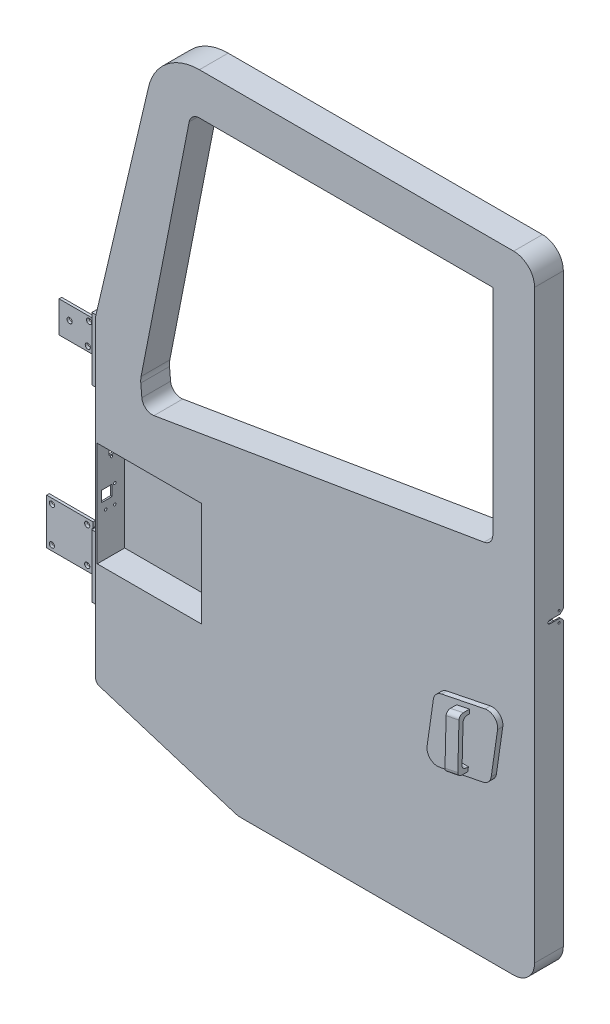
SolidWorks part; units mm, degrees
ref_plane "Front Plane" through (0, 0, 0) normal (0, 0, 1) x (1, 0, 0)
ref_plane "Top Plane" through (0, 0, 0) normal (0, 1, 0) x (1, 0, 0)
ref_plane "Right Plane" through (0, 0, 0) normal (1, 0, 0) x (0, 0, -1)
sketch "Sketch2" plane through (0, 0, 0) normal (0, 0, 1) x (1, 0, 0)
  line L1 (-179.7693, -762.022) -> (482.6, -762.022)
  line L3 (-281.2299, 761.978) -> (482.6, 761.978)
  line L4 (533.4, -711.222) -> (533.4, 711.178)
  line L5 (-459.8603, -656.939) -> (-452.0517, -645.784) construction
  line L6 (-417.9715, 597.0829) -> (44.2876, -63.266) construction
  line L8 (-524.4721, -657.2008) -> (-194.8579, -759.7295)
  line L9 (-306.1723, 639.7777) -> (-423.0219, 45.4039)
  line L10 (-423.7768, 31.1096) -> (-421.1458, 1.4921)
  line L14 (-281.2299, 660.378) -> (431.8, 660.378)
  line L16 (431.7996, 138.4174) -> (431.8, 660.378)
  line L17 (431.8, -660.422) -> (431.8, 660.378) construction
  line L18 (-172.0509, -660.422) -> (431.8, -660.422) construction
  line L19 (-533.4, 116.926) -> (-405.8883, 659.253)
  line L20 (-367.7549, -599.547) -> (-172.0509, -660.422) construction
  line L21 (-55.7209, -79.6007) -> (521.0599, 744.3665) construction
  line L22 (-306.1723, 639.7777) -> (-424.4164, 38.3105) construction
  line L23 (-424.4164, 38.3105) -> (-367.7549, -599.547) construction
  line L24 (-414.3579, -691.4526) -> (-194.8579, -759.7295) construction
  line L25 (-179.7693, -762.022) -> (482.6, -762.022)
  line L27 (-281.2299, 761.978) -> (482.6, 761.978)
  line L28 (533.4, -711.222) -> (533.4, 711.178)
  line L29 (-459.8603, -656.939) -> (-452.0517, -645.784) construction
  line L30 (-417.9715, 597.0829) -> (44.2876, -63.266) construction
  line L31 (-533.4, 116.926) -> (-466.2749, -638.723) construction
  line L32 (-391.6402, -21.3099) -> (410.6048, 113.3679)
  line L33 (-55.7209, -79.6007) -> (521.0599, 744.3665) construction
  line L34 (-281.2299, 761.978) -> (482.6, 761.978)
  line L35 (-533.4, 116.926) -> (-533.4, -645.074)
  line L36 (-179.7693, -762.022) -> (482.6, -762.022)
  line L37 (533.4, 711.178) -> (533.4, -711.222)
  line L38 (-417.9715, 597.0829) -> (44.2876, -63.266) construction
  line L39 (-471.5639, -673.6583) -> (-452.0517, -645.784) construction
  line L40 (-405.8883, 659.253) -> (-528.8132, 33.9764) construction
  line L41 (-55.7209, -79.6007) -> (521.0599, 744.3665) construction
  arc A0 (-405.8883, 659.253) -> (-281.2299, 761.978) centre (-281.2299, 634.978) cw
  arc A3 (533.4, 711.178) -> (482.6, 761.978) centre (482.6, 711.178) ccw
  arc A4 (482.6, -762.022) -> (533.4, -711.222) centre (482.6, -711.222) ccw
  arc A5 (-194.8579, -759.7295) -> (-179.7693, -762.022) centre (-179.7693, -711.222) ccw
  arc A7 (-367.7549, -599.547) -> (-367.7549, -599.547) centre (-367.7549, -599.547) ccw
  arc A8 (-172.0509, -660.422) -> (-172.0509, -660.422) centre (-172.0509, -660.422) ccw
  arc A9 (431.8, -660.422) -> (431.8, -660.422) centre (431.8, -660.422) ccw
  arc A10 (431.8, 660.378) -> (431.8, 660.378) centre (431.8, 660.378) ccw
  arc A11 (-306.1723, 639.7777) -> (-281.2299, 660.378) centre (-281.2299, 634.978) cw
  arc A12 (-423.0219, 45.4039) -> (-423.7768, 31.1096) centre (-373.176, 35.6045) ccw
  arc A13 (-424.4164, 38.3105) -> (-424.4164, 38.3105) centre (-424.4164, 38.3105) ccw construction
  arc A16 (-466.2749, -638.723) -> (-414.3579, -691.4526) centre (-391.0208, -616.5518) ccw construction
  arc A17 (-533.4, -645.074) -> (-524.4721, -657.2008) centre (-520.7, -645.074) ccw
  arc A18 (-528.8132, 33.9764) -> (-533.4, 116.926) centre (-501.9071, 77.0658) ccw construction
  arc A19 (431.7996, 138.4174) -> (410.6048, 113.3679) centre (406.3996, 138.4174) cw
  arc A20 (-391.6402, -21.3099) -> (-421.1458, 1.4921) centre (-395.8454, 3.7395) cw
  point P0 (0, 0)
  point P16 (-533.4, -0.0244)
  point P56 (0, 0)
  point P61 (0, 0)
  dimension "D3" = 127
  dimension "D6" = 50.8
  dimension "D8" = 50.8
  dimension "D2" = 12.7
  dimension "D9" = 25.4
  dimension "D1" = 1066.8
  dimension "D4" = 1524
  dimension "D5" = 762
  dimension "D7" = 101.6
extrude "Boss-Extrude1" add sketch "Sketch2" along normal mid plane 69.85 contours L8 A5 L1 A4 L4 A3 L3 A0 L10 A12 L9 A11 L14 L16 A20 region at (22.1716, -171.0663, 0)
ref_plane "bottom" through (0, -762.022, 0) normal (0, -1, 0) x (-1, 0, 0)
ref_plane "top door check" through (0, -158.772, 0) normal (0, -1, 0) x (-1, 0, 0)
ref_plane "door check mid" through (0, -176.2345, 0) normal (0, -1, 0) x (-1, 0, 0)
ref_plane "bottom door check" through (0, -193.697, 0) normal (0, -1, 0) x (-1, 0, 0)
ref_plane "top hinge top hole" through (0, 66.653, 0) normal (0, -1, 0) x (-1, 0, 0)
ref_plane "top hinge middle hole" through (0, 44.428, 0) normal (0, -1, 0) x (-1, 0, 0)
ref_plane "top hinge bottom hole" through (0, 12.678, 0) normal (0, -1, 0) x (-1, 0, 0)
ref_plane "bottome hinge top hole" through (0, -363.5595, 0) normal (0, -1, 0) x (-1, 0, 0)
ref_plane "bottom hinge bottom hole" through (0, -449.2845, 0) normal (0, -1, 0) x (-1, 0, 0)
ref_plane "Plane1" through (0, 0, 31.75) normal (0, 0, 1) x (1, 0, 0)
sketch "Sketch3" plane through (0, 0, 34.925) normal (0, 0, 1) x (1, 0, 0)
  line L0 (320.1959, -245.101) -> (425.9265, -223.6716)
  line L3 (314.9201, -401.6691) -> (420.6507, -380.2397)
  line L4 (456.113, -252.1835) -> (440.7462, -358.9639)
  line L5 (300.1004, -266.3768) -> (284.7336, -373.1572)
  line L6 (310.4001, -194.8067) -> (287.3499, -354.9772) construction
  line L7 (-487.6326, -408.8312) -> (533.4008, -201.8888) construction
  line L8 (-457.3598, -558.1943) -> (563.6737, -351.2518) construction
  line L9 (461.2461, -216.515) -> (438.1959, -376.6855) construction
  line L10 (373.0612, -234.3863) -> (367.7854, -390.9544) construction
  line L11 (360.2667, -236.9795) -> (354.9908, -393.5476)
  line L12 (385.8558, -231.7931) -> (380.58, -388.3612)
  line L13 (360.3684, -233.9586) -> (355.0926, -390.5267) construction
  line L14 (385.754, -234.814) -> (380.4782, -391.3821) construction
  arc A0 (300.1004, -266.3768) -> (320.1959, -245.101) centre (325.2414, -269.9949) cw
  arc A1 (284.7336, -373.1572) -> (314.9201, -401.6691) centre (309.8746, -376.7752) ccw
  arc A2 (440.7462, -358.9639) -> (420.6507, -380.2397) centre (415.6052, -355.3458) cw
  arc A3 (456.113, -252.1835) -> (425.9265, -223.6716) centre (430.972, -248.5655) ccw
  dimension "D3" = 25.4
  dimension "D1" = 152.4
  dimension "D2" = 152.4
  dimension "D4" = 12.7
  dimension "D5" = 12.7
extrude "Boss-Extrude2" add sketch "Sketch3" along normal blind 12.7 contours L5 A1 L3 L11 L0 A0 | L4 A3 L0 L12 L3 A2 | L12 L0 L11 L3 region at (325.2101, -323.7797, 34.925) region at (370.4233, -312.6704, 34.925) region at (415.6365, -301.561, 34.925)
sketch "Sketch5" plane through (0, 0, 34.925) normal (0, 0, 1) x (1, 0, 0)
  line L6 (-179.7693, -762.022) -> (482.6, -762.022)
  line L12 (-179.7693, -762.022) -> (482.6, -762.022)
  line L28 (387.9598, -243.0291) -> (384.7172, -375.8602)
  line L29 (353.4927, -382.1888) -> (356.7353, -249.3577)
  line L30 (387.9598, -243.0291) -> (356.7353, -249.3577)
  line L31 (384.7172, -375.8602) -> (353.4927, -382.1888)
  line L32 (320.1959, -245.101) -> (425.9265, -223.6716) construction
  line L33 (314.9201, -401.6691) -> (420.6507, -380.2397) construction
  line L34 (320.1959, -245.101) -> (425.9265, -223.6716) construction
  line L35 (314.9201, -401.6691) -> (420.6507, -380.2397) construction
  dimension "D2" = 11.43
  dimension "D3" = 11.43
  dimension "D1" = 0
extrude "Boss-Extrude4" add sketch "Sketch5" along normal blind 38.1 contours L31 L28 L30 L29 region at (370.7262, -312.609, 34.925)
sketch "Sketch6" plane through (393.6581, -9.61, 0) normal (0.9997, -0.0244, 0) x (0, 0, -1)
  line L9 (-47.625, -356.1994) -> (-62.865, -356.1994)
  line L10 (-62.865, -356.1994) -> (-62.865, -243.6487)
  line L11 (-62.865, -243.6487) -> (-47.625, -243.6487)
  line L12 (-47.625, -356.1994) -> (-62.865, -356.1994)
  line L13 (-62.865, -356.1994) -> (-62.865, -243.6487)
  line L14 (-62.865, -243.6487) -> (-47.625, -243.6487)
  line M5 (-47.625, -366.3594) -> (-47.625, -233.4887)
  dimension "D1" = 10.16
extrude "Cut-Extrude6" cut sketch "Sketch6" against normal through all and the other way through all contours L14 L13 L12 M5 region at (386.3385, -309.4447, 55.245)
fillet "Fillet5" radius 10.16 4 edges at (369.1049, -379.0245, 73.025) (369.4394, -365.3242, 62.865) (372.1861, -252.8071, 62.865) (372.3476, -246.1934, 73.025)
sketch "Sketch7" plane through (-533.4, 59.3738, 0) normal (1, 0, 0) x (0, 0, 1)
  line L0 (0, 821.3958) -> (0, -702.6042) construction
  line L1 (34.925, 821.3958) -> (-34.925, 821.3958) construction
  line L2 (34.925, -702.6042) -> (-34.925, -702.6042) construction
  line L4 (-31.75, -57.5522) -> (31.75, -57.5522)
  line L5 (-31.75, -57.5522) -> (-31.75, 94.8478)
  line L6 (-31.75, 94.8478) -> (31.75, 94.8478)
  line L11 (31.75, -57.5522) -> (31.75, 94.8478)
  line L12 (-31.75, -57.5522) -> (31.75, 94.8478) construction
  line L13 (-31.75, 94.8478) -> (31.75, -57.5522) construction
  line L19 (34.925, -57.5522) -> (-34.925, -57.5522) construction
  line L21 (-31.75, 552.0478) -> (31.75, 552.0478)
  line L28 (-31.75, 552.0478) -> (-31.75, 399.6478)
  line L29 (-31.75, 399.6478) -> (31.75, 399.6478)
  line L30 (31.75, 552.0478) -> (31.75, 399.6478)
  line L31 (-31.75, 552.0478) -> (31.75, 399.6478) construction
  line L32 (-31.75, 399.6478) -> (31.75, 552.0478) construction
  point P6 (0, 18.6478)
  point P13 (0, 475.8478)
  dimension "D1" = 63.5
  dimension "D2" = 152.4
  dimension "D4" = 304.8
extrude "Boss-Extrude5" add sketch "Sketch7" against normal blind 12.7
sketch "Sketch16" plane through (0, 0, 34.925) normal (0, 0, 1) x (1, 0, 0)
  line L1 (-529.59, -148.3099) -> (-529.59, -402.3099)
  line L3 (-275.59, -402.3099) -> (-275.59, -148.3099)
  line L5 (-533.4, 116.926) -> (-533.4, -645.074) construction
  line L6 (-529.59, -148.3099) -> (-275.59, -148.3099)
  line L7 (-529.59, -402.3099) -> (-275.59, -402.3099)
  dimension "D1" = 254
  dimension "D2" = 127
  dimension "D3" = 254
  dimension "D4" = 3.81
extrude "Cut-Extrude8" cut sketch "Sketch16" against normal blind 66.675
sketch "Sketch20" plane through (-533.4, 0, 0) normal (-1, 0, 0) x (0, 0, 1)
  line L0 (-38.4175, -176.2345) -> (38.4175, -176.2345) construction
  line L1 (-6.35, -188.9345) -> (6.35, -188.9345)
  line L2 (-6.35, -188.9345) -> (-6.35, -163.5345)
  line L3 (-6.35, -163.5345) -> (6.35, -163.5345)
  line L4 (6.35, -188.9345) -> (6.35, -163.5345)
  line L5 (-6.35, -188.9345) -> (6.35, -163.5345) construction
  line L6 (-6.35, -163.5345) -> (6.35, -188.9345) construction
  line L7 (-38.4175, -158.772) -> (38.4175, -158.772) construction
  line L8 (6.35, -176.2345) -> (-6.35, -176.2345) construction
  circle A0 centre (0, -158.772) radius 2.54
  circle A1 centre (0, -193.697) radius 2.54
  point P0 (0, -176.2345)
  dimension "D3" = 5.08
  dimension "D1" = 12.7
  dimension "D2" = 25.4
extrude "Cut-Extrude12" cut sketch "Sketch20" against normal up to surface (3.81 mm away) contours A0 | L4 L3 L2 L1 | A1 up to face at (-529.59, -275.3099, 1.5875)
sketch "Sketch21" plane through (0, 0, 0) normal (0, 0, 1) x (1, 0, 0)
  line L0 (-38.4175, 66.653) -> (38.4175, 66.653) construction
  line L1 (-202.423, 66.653) -> (-1027.3811, 66.653) construction
  line L2 (-212.5576, 44.428) -> (-1027.3811, 44.428) construction
  line L3 (-38.4175, 44.428) -> (38.4175, 44.428) construction
  line L4 (-212.5576, 12.678) -> (-1027.3811, 12.678) construction
  line L5 (-38.4175, 12.678) -> (38.4175, 12.678) construction
  line L6 (-546.1, 116.926) -> (-546.1, -35.474) construction
  line L7 (-558.8, 66.653) -> (-546.1, 66.653)
  line L8 (-558.8, 66.653) -> (-558.8, 12.678)
  line L9 (-558.8, 12.678) -> (-546.1, 12.678)
  line L10 (-546.1, 66.653) -> (-546.1, 12.678)
  line L11 (-654.05, 77.448) -> (-654.05, 1.248)
  line L12 (-654.05, 77.448) -> (-558.8, 77.448)
  line L15 (-558.8, 77.448) -> (-558.8, 12.678)
  line L16 (-654.05, 77.448) -> (-558.8, 12.678) construction
  line L17 (-654.05, 10.0872) -> (-558.8, 77.448) construction
  line L18 (-654.05, 1.248) -> (-558.8, 1.248)
  line L19 (-558.8, 12.678) -> (-558.8, 1.248)
  circle A0 centre (-584.2, 12.678) radius 6.35
  circle A1 centre (-628.65, 44.428) radius 6.35
  circle A2 centre (-581.025, 66.653) radius 6.35
  point P18 (-605.4912, 44.428)
  dimension "D2" = 12.7
  dimension "D3" = 25.4
  dimension "D4" = 69.85
  dimension "D5" = 22.225
  dimension "D6" = 95.25
  dimension "D9" = 64.77
  dimension "D1" = 12.7
  dimension "D7" = 76.2
  dimension "D8" = 33.02
extrude "Boss-Extrude8" add sketch "Sketch21" along normal mid plane 6.35 contours L19 L8 L15 L12 L11 L18 A2 A1 A0 | L10 L7 L8 L9 region at (-552.45, 39.6655, 0) region at (-606.8928, 39.2427, 0)
sketch "Sketch26" plane through (0, 0, 0) normal (0, 0, 1) x (1, 0, 0)
  line L0 (-193.6896, -363.5595) -> (-881.8717, -363.5595) construction
  line L1 (-38.4175, -363.5595) -> (38.4175, -363.5595) construction
  line L2 (-133.4597, -449.2845) -> (-881.8717, -449.2845) construction
  line L3 (-38.4175, -449.2845) -> (38.4175, -449.2845) construction
  line L4 (-625.8948, -363.5595) -> (-625.8948, -449.2845) construction
  line L5 (-625.8948, -406.422) -> (-892.4677, -406.422) construction
  line L6 (-546.1, -340.274) -> (-546.1, -492.674) construction
  line L7 (-571.5, -449.2845) -> (-546.1, -449.2845)
  line L8 (-571.5, -449.2845) -> (-571.5, -363.5595)
  line L9 (-571.5, -363.5595) -> (-546.1, -363.5595)
  line L10 (-546.1, -449.2845) -> (-546.1, -363.5595)
  line L11 (-571.5, -449.2845) -> (-546.1, -363.5595) construction
  line L12 (-571.5, -363.5595) -> (-546.1, -449.2845) construction
  point P12 (-558.8, -406.422)
  dimension "D1" = 25.4
extrude "Boss-Extrude12" add sketch "Sketch26" along normal mid plane 12.7
sketch "Sketch27" plane through (0, 0, 0) normal (0, 0, 1) x (1, 0, 0)
  line L0 (-211.2814, -363.5595) -> (-919.4505, -363.5595) construction
  line L1 (-38.4175, -363.5595) -> (38.4175, -363.5595) construction
  line L2 (-201.3631, -449.2845) -> (-928.7076, -449.2845) construction
  line L3 (-38.4175, -449.2845) -> (38.4175, -449.2845) construction
  line L4 (-571.5, -363.5595) -> (-571.5, -449.2845) construction
  line L5 (-631.7994, -363.5595) -> (-631.7994, -449.2845) construction
  line L6 (-631.7994, -406.422) -> (-919.4505, -406.422) construction
  line L8 (-684.2125, -461.9845) -> (-571.5, -461.9845)
  line L9 (-684.2125, -461.9845) -> (-684.2125, -350.8595)
  line L10 (-684.2125, -350.8595) -> (-571.5, -350.8595)
  line L11 (-571.5, -461.9845) -> (-571.5, -350.8595)
  line L12 (-684.2125, -461.9845) -> (-571.5, -350.8595) construction
  line L13 (-684.2125, -350.8595) -> (-571.5, -461.9845) construction
  circle A0 centre (-585.7875, -363.5595) radius 6.35
  circle A2 centre (-671.5125, -449.2845) radius 6.35
  circle A4 centre (-585.7875, -449.2845) radius 6.35
  circle A5 centre (-671.5125, -363.5595) radius 6.35
  point P22 (-627.8563, -406.422)
  dimension "D1" = 12.7
  dimension "D2" = 100.0125
  dimension "D3" = 14.2875
  dimension "D4" = 12.7
extrude "Boss-Extrude13" add sketch "Sketch27" along normal mid plane 6.35
sketch "Sketch28" plane through (-533.4, 0, 0) normal (-1, 0, 0) x (0, 0, 1)
  line L4 (24.765, -252.697) -> (24.765, -278.697)
  line L5 (34.925, -245.101) -> (34.925, -223.6716) construction
  line L6 (-38.4175, -193.697) -> (38.4175, -193.697) construction
  line L8 (24.765, -278.697) -> (-1.235, -278.697)
  line L9 (24.765, -278.697) -> (24.765, -252.697)
  line L10 (24.765, -252.697) -> (-1.235, -252.697)
  line L11 (-1.235, -278.697) -> (-1.235, -252.697)
  circle A7 centre (-7.705, -253.397) radius 3
  circle A8 centre (-7.705, -298.397) radius 3
  circle A9 centre (14.375, -298.397) radius 3
  point P16 (24.765, -265.697)
  dimension "D4" = 45
  dimension "D5" = 26
  dimension "D2" = 26
  dimension "D3" = 22.08
  dimension "D8" = 10.16
  dimension "D7" = 6
  dimension "D10" = 72
extrude "Cut-Extrude13" cut sketch "Sketch28" against normal up to surface (3.81 mm away) contours L4 | A8 | A9 | A7 region at (-533.4, -265.697, 11.765) region at (-533.4, -298.397, -7.705) region at (-533.4, -298.397, 14.375) up to face at (-529.59, -176.2345, 0)
sketch "Sketch29" plane through (533.4, 0, 0) normal (1, 0, 0) x (0, 0, -1)
  line L0 (34.925, -762.022) -> (34.925, -15.897)
  line L1 (34.925, -711.222) -> (34.925, 711.178) construction
  line L2 (27.305, -15.897) -> (1.9385, -15.897)
  line L3 (34.925, -0.022) -> (34.925, -23.517)
  line L4 (1.9385, -7.642) -> (27.305, -7.642)
  line L5 (27.305, -7.642) -> (34.925, -0.022)
  line L6 (27.305, -15.897) -> (34.925, -23.517)
  arc A0 (1.9385, -7.642) -> (1.9385, -15.897) centre (1.9385, -11.7695) ccw
  line M2 (34.925, -711.222) -> (34.925, 711.178)
extrude "Cut-Extrude14" cut sketch "Sketch29" against normal blind 2.54 contours L4 A0 L2 L6 L0 L5 M2 region at (533.4, -11.7695, -19.3332)
sketch "Sketch30" plane through (0, 0, -34.925) normal (0, 0, -1) x (-1, 0, 0)
  line L0 (-530.86, -11.7695) -> (-530.86, 13.6305)
  line L1 (-530.86, -23.517) -> (-530.86, -0.022) construction
  line L2 (-530.86, 13.6305) -> (-505.46, 13.6305)
  line L3 (-505.46, 13.6305) -> (-505.46, -37.1695)
  line L4 (-505.46, -37.1695) -> (-530.86, -37.1695)
  line L5 (-530.86, -37.1695) -> (-530.86, -11.7695)
extrude "Cut-Extrude15" cut sketch "Sketch30" against normal blind 38.1
sketch "Sketch31" plane through (533.4, 0, 0) normal (1, 0, 0) x (0, 0, -1)
  line L0 (34.925, -11.7695) -> (34.925, 0.9305)
  line L1 (34.925, -37.1695) -> (34.925, 13.6305) construction
  line L2 (34.925, -0.022) -> (34.925, 711.178) construction
  line L3 (34.925, 0.9305) -> (24.765, 0.9305)
  line L4 (24.765, 0.9305) -> (24.765, -24.4695)
  circle A0 centre (24.765, 0.9305) radius 2.54
  circle A1 centre (24.765, -24.4695) radius 2.54
extrude "Cut-Extrude16" cut sketch "Sketch31" against normal blind 10.668 contours L4 A0 L3 | L3 A0 L4 | A1 region at (533.4, -0.1475, -25.843) region at (533.4, 1.2898, -24.4057) region at (533.4, -22.7243, -26.5103)
equation "\"doorwidth\"= 42in"
equation "\"D1@Sketch2\"=\"doorwidth\""
equation "\"doorheight\"= 60in"
equation "\"D4@Sketch2\"=\"doorheight\""
equation "\"doorthickness\"= 2.75in"
equation "\"D1@Boss-Extrude1\"=\"doorthickness\""
equation "\"hingewidth\"= 2.5in"
equation "\"hingeheight\"= 6in"
equation "\"distanceofhinges\"= 12in"
equation "\"D1@Sketch7\"=\"hingewidth\""
equation "\"D2@Sketch7\"=\"hingeheight\""
equation "\"D4@Sketch7\"=\"distanceofhinges\""
